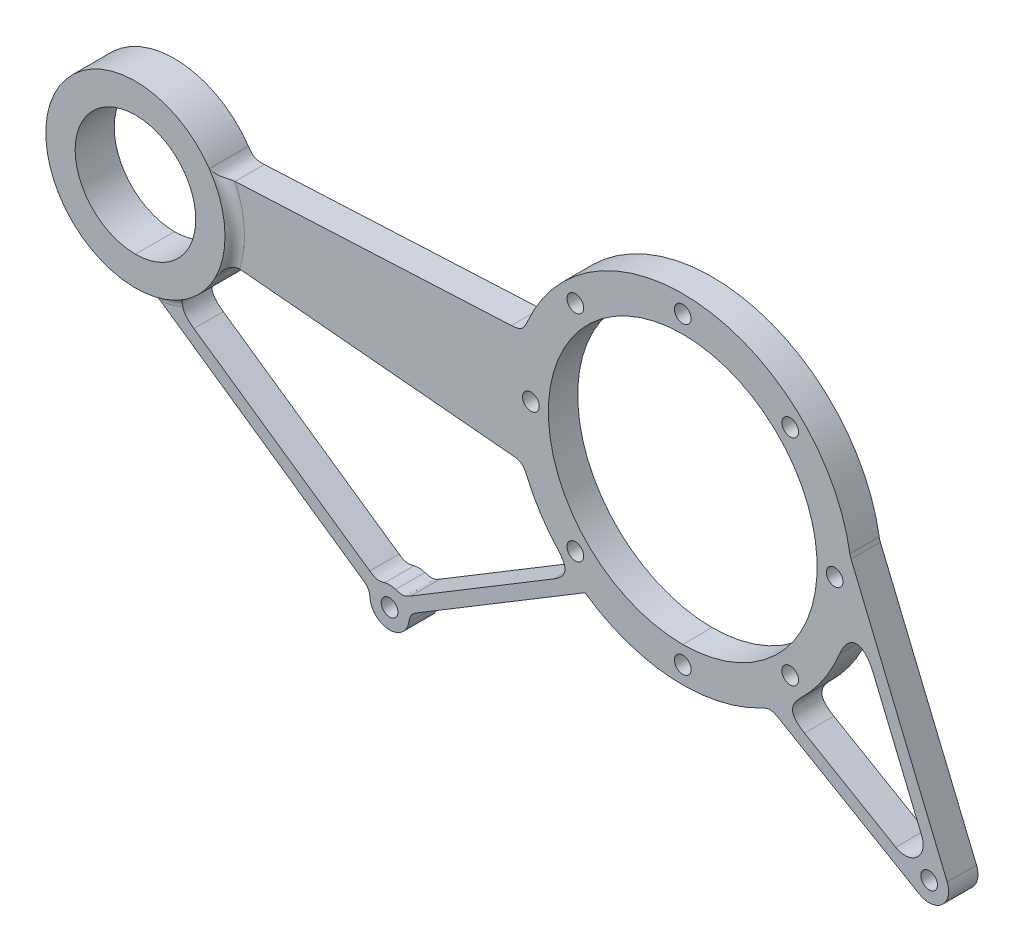
SolidWorks part; units mm, degrees
material "6061-T6 (SS)"
ref_plane "Front Plane" through (0, 0, 0) normal (0, 0, 1) x (1, 0, 0)
ref_plane "Top Plane" through (0, 0, 0) normal (0, 1, 0) x (1, 0, 0)
ref_plane "Right Plane" through (0, 0, 0) normal (1, 0, 0) x (0, 0, -1)
sketch "Sketch1" plane through (0, 0, 0) normal (0, 0, 1) x (1, 0, 0)
  line L0 (-329.0358, 136.1378) -> (-124.1059, 166.9079)
  line L1 (-343.7594, 72.9056) -> (-234.0298, -3.2296)
  line L2 (-223.6766, -3.5577) -> (-149.0272, 41.5159)
  line L3 (-114.3, 88.9) -> (-114.3, 101.6) construction
  line L4 (-53.3056, 126.9173) -> (-9.4675, 21.3025)
  line L5 (-23.0618, 9.4221) -> (-78.8665, 41.9532)
  circle A0 centre (-114.3, 88.9) radius 82.9716 construction
  circle A1 centre (-228.6, -20.8038) radius 12.7 construction
  circle A2 centre (0, 0) radius 12.7 construction
  circle A3 centre (-323.85, 101.6) radius 114 construction
  circle A4 centre (-323.85, 101.6) radius 23.5
  circle A5 centre (-114.3, 101.6) radius 52.3875
  arc A6 (-142.4404, 41.8555) -> (-85.4371, 42.2012) centre (-114.3, 101.6) ccw
  circle A7 centre (-323.85, 101.6) radius 34.925
  arc A8 (-223.6766, -3.5577) -> (-234.0298, -3.2296) centre (-228.6, 4.5962) cw
  arc A9 (-9.4675, 21.3025) -> (-23.0618, 9.4221) centre (-18.2648, 17.651) cw
  circle A10 centre (-228.6, 4.5962) radius 3.2512
  circle A11 centre (-18.2648, 17.651) radius 3.2512
  arc A12 (-142.4404, 41.8555) -> (-149.0272, 41.5159) centre (-145.4168, 35.5364) ccw
  arc A13 (-78.8665, 41.9532) -> (-85.4371, 42.2012) centre (-82.3843, 35.9187) ccw
  circle A14 centre (-114.3, 101.6) radius 66.04 construction
  arc A15 (-124.1059, 166.9079) -> (-53.3056, 126.9173) centre (-114.3, 101.6) cw
  dimension "D1" = 88.9
  dimension "D2" = 12.7
  dimension "D3" = 25.4
  dimension "D4" = 25.4
  dimension "D8" = 165.9433
  dimension "D9" = 228
  dimension "D10" = 47
  dimension "D12" = 104.775
  dimension "D14" = 132.08
  dimension "D15" = 69.85
  dimension "D16" = 9.525
  dimension "D18" = 9.525
  dimension "D20" = 6.5024
  dimension "D21" = 6.5024
  dimension "D23" = 6.985
  dimension "D24" = 6.985
  dimension "D25" = 66.04
  dimension "D5" = 228.6
  dimension "D6" = 20.8038
  dimension "D7" = 114.3
  dimension "D11" = 12.7
  dimension "D13" = 209.55
  dimension "D17" = 25.4
  dimension "D19" = 25.4
  dimension "D22" = 17.651
extrude "Boss-Extrude1" add sketch "Sketch1" along normal blind 11.43 contours A7 A4 | A8 L2 A6 L0 A7 L1 A10 | A6 A5 | A9 L4 A6 L5 A11 region at (-187.4243, 81.6254, 0) region at (-301.706, 127.3172, 0)
ref_point "Point4"
sketch "Sketch5" plane through (0, 0, 11.43) normal (0, 0, 1) x (1, 0, 0)
  circle A0 centre (-323.85, 101.6) radius 23.5
  circle A1 centre (-323.85, 101.6) radius 34.925
  circle A4 centre (-323.85, 101.6) radius 23.5 construction
  arc A5 (-329.0358, 136.1378) -> (-343.7594, 72.9056) centre (-323.85, 101.6) ccw construction
extrude "Boss-Extrude4" add sketch "Sketch5" along normal blind 3.81
ref_plane "Plane1" through (-114.3, 101.6, 0) normal (-1, 0, 0) x (0, 0, 1)
ref_plane "Plane2" through (-323.85, 0, 0) normal (-1, 0, 0) x (0, 0, 1)
split line "Split Line1"
split line "Split Line2"
sketch "Sketch8" plane through (0, 0, 11.43) normal (0, 0, 1) x (1, 0, 0)
  line L0 (-114.3, 101.6) -> (-114.3, 160.8137) construction
  circle A0 centre (-114.3, 101.6) radius 59.2137 construction
  circle A1 centre (-114.3, 160.8137) radius 3.2512
  circle A2 centre (-72.4296, 143.4704) radius 3.2512
  circle A3 centre (-55.0862, 101.6) radius 3.2512
  circle A4 centre (-72.4296, 59.7296) radius 3.2512
  circle A5 centre (-114.3, 42.3863) radius 3.2512
  circle A6 centre (-156.1704, 59.7296) radius 3.2512
  circle A7 centre (-173.5137, 101.6) radius 3.2512
  circle A8 centre (-156.1704, 143.4704) radius 3.2512
  point P22 (-114.3, 101.6)
  dimension "D1" = 118.4275
  dimension "D2" = 6.5024
  dimension "D3" = 8
extrude "Cut-Extrude3" cut sketch "Sketch8" against normal through all both and the other way through all
sketch "Sketch9" plane through (0, 0, 0) normal (0, 0, -1) x (-1, 0, 0)
  line L0 (48.4248, 96.938) -> (21.1243, 31.1656)
  line L1 (31.2747, 22.2949) -> (75.5642, 48.1133)
  line L2 (18.2648, 17.651) -> (64.5869, 44.6542) construction
  line L3 (23.0618, 9.4221) -> (78.8665, 41.9532) construction
  line L4 (53.3056, 126.9173) -> (9.4675, 21.3025) construction
  line L5 (18.2648, 17.651) -> (30.1686, 46.3295) construction
  line L6 (11.227, 20.5722) -> (49.028, 111.6426)
  line L7 (22.1024, 11.0679) -> (80.2923, 44.9894)
  line L8 (53.3056, 126.9173) -> (9.4675, 21.3025)
  line L9 (78.8665, 41.9532) -> (23.0618, 9.4221)
  arc A0 (53.3056, 126.9173) -> (49.028, 111.6426) centre (114.3, 101.6) ccw
  arc A1 (85.4371, 42.2012) -> (142.4404, 41.8555) centre (114.3, 101.6) ccw construction
  arc A2 (80.2923, 44.9894) -> (85.4371, 42.2012) centre (114.3, 101.6) ccw
  arc A4 (48.4248, 96.938) -> (75.5642, 48.1133) centre (114.3, 101.6) ccw
  arc A7 (85.4371, 42.2012) -> (78.8665, 41.9532) centre (82.3843, 35.9187) ccw construction
  arc A8 (11.227, 20.5722) -> (22.1024, 11.0679) centre (18.2648, 17.651) ccw
  arc A9 (78.8665, 41.9532) -> (85.4371, 42.2012) centre (82.3843, 35.9187) cw
  arc A10 (23.0618, 9.4221) -> (9.4675, 21.3025) centre (18.2648, 17.651) cw
  arc A11 (21.1243, 31.1656) -> (31.2747, 22.2949) centre (27.6929, 28.4392) ccw
  point P39 (39.1342, 32.7568)
  point P40 (0, 0)
  dimension "D1" = 7.62
  dimension "D2" = 5.08
  dimension "D4" = 7.112
  dimension "D3" = 5.08
extrude "Cut-Extrude5" cut sketch "Sketch9" against normal up to surface (11.43 mm away) up to face at (-111.0488, 160.8137, 11.43)
sketch "Sketch10" plane through (0, 0, 0) normal (0, 0, -1) x (-1, 0, 0)
  line L0 (323.8812, 77.8778) -> (-49198.7404, -6814.8686) construction
  line L1 (237.8465, 11.0118) -> (309.7494, 60.9012) construction
  line L2 (221.7813, 8.7133) -> (158.5805, 46.8743) construction
  line L3 (152.385, 47.6481) -> (221.137, 6.1352)
  line L4 (322.5609, 66.6988) -> (235.9505, 6.6047)
  line L5 (149.0272, 41.5159) -> (223.6766, -3.5577)
  line L6 (343.7594, 72.9056) -> (234.0298, -3.2296)
  line L8 (315.188, 67.7662) -> (233.0546, 10.7785)
  line L9 (156.7056, 50.9735) -> (223.7628, 10.484)
  line L10 (301.5001, 74.7627) -> (161.3478, 55.2558)
  line L11 (223.6766, -3.5577) -> (149.0272, 41.5159) construction
  line L12 (343.7594, 72.9056) -> (234.0298, -3.2296) construction
  arc A0 (161.3478, 55.2558) -> (156.7056, 50.9735) centre (114.3, 101.6) cw
  circle A2 centre (323.85, 101.6) radius 34.925 construction
  arc A3 (315.188, 67.7662) -> (301.5001, 74.7627) centre (323.85, 101.6) cw
  arc A4 (221.137, 6.1352) -> (235.9505, 6.6047) centre (228.6, 4.5962) ccw
  circle A5 centre (228.6, 4.5962) radius 3.2512 construction
  arc A6 (142.4404, 41.8555) -> (152.385, 47.6481) centre (114.3, 101.6) ccw
  circle A7 centre (323.85, 101.6) radius 23.5 construction
  arc A9 (80.2923, 44.9894) -> (142.4404, 41.8555) centre (114.3, 101.6) ccw construction
  arc A10 (149.0272, 41.5159) -> (142.4404, 41.8555) centre (145.4168, 35.5364) ccw construction
  arc A11 (322.5609, 66.6988) -> (343.7594, 72.9056) centre (323.85, 101.6) ccw
  arc A12 (142.4404, 41.8555) -> (149.0272, 41.5159) centre (145.4168, 35.5364) cw
  arc A13 (233.0546, 10.7785) -> (223.7628, 10.484) centre (228.6, 4.5962) ccw
  arc A14 (223.6766, -3.5577) -> (234.0298, -3.2296) centre (228.6, 4.5962) ccw construction
  arc A15 (223.6766, -3.5577) -> (234.0298, -3.2296) centre (228.6, 4.5962) ccw
  arc A16 (114.3, 49.2125) -> (114.3, 153.9875) centre (114.3, 101.6) ccw construction
  dimension "D1" = 7.62
  dimension "D2" = 66.04
  dimension "D3" = 0
  dimension "D4" = 5.08
  dimension "D5" = 5.08
extrude "Cut-Extrude6" cut sketch "Sketch10" against normal up to surface (11.43 mm away) up to face at (-41.9462, 47.9637, 11.43)
sketch "Sketch12" plane through (0, 0, 0) normal (0, 0, -1) x (-1, 0, 0)
  line L0 (329.0358, 136.1378) -> (124.1059, 166.9079) construction
  line L1 (161.3478, 147.9442) -> (301.5001, 128.4373)
  line L2 (121.5219, 153.4873) -> (327.0896, 124.8756) construction
  line L3 (124.1059, 166.9079) -> (329.0358, 136.1378)
  arc A0 (114.3, 49.2125) -> (114.3, 153.9875) centre (114.3, 101.6) ccw construction
  arc A1 (161.3478, 147.9442) -> (124.1059, 166.9079) centre (114.3, 101.6) ccw
  arc A3 (329.0358, 136.1378) -> (301.5001, 128.4373) centre (323.85, 101.6) ccw
  circle A4 centre (323.85, 101.6) radius 34.925 construction
  circle A6 centre (323.85, 101.6) radius 23.5 construction
  arc A7 (156.7056, 50.9735) -> (161.3478, 55.2558) centre (114.3, 101.6) ccw construction
  dimension "D1" = 0
extrude "Cut-Extrude8" cut sketch "Sketch12" against normal up to surface (11.43 mm away) up to face at (-41.9462, 47.9637, 11.43)
sketch "Sketch15" plane through (0, 0, 0) normal (0, 0, -1) x (-1, 0, 0)
  line L0 (176.5285, 79.489) -> (290.922, 89.9596)
  line L2 (301.5001, 74.7627) -> (161.3478, 55.2558)
  line L3 (161.3478, 147.9442) -> (301.5001, 128.4373)
  line L4 (161.3478, 147.9442) -> (301.5001, 128.4373) construction
  line L5 (176.5285, 123.711) -> (293.0538, 118.0727)
  arc A0 (176.5285, 79.489) -> (161.3478, 55.2558) centre (114.3, 101.6) cw
  arc A2 (290.922, 89.9596) -> (301.5001, 74.7627) centre (323.85, 101.6) ccw
  arc A4 (80.2923, 44.9894) -> (152.385, 47.6481) centre (114.3, 101.6) ccw construction
  circle A5 centre (323.85, 101.6) radius 34.925 construction
  arc A6 (161.3478, 147.9442) -> (176.5285, 123.711) centre (114.3, 101.6) cw
  arc A7 (301.5001, 128.4373) -> (293.0538, 118.0727) centre (323.85, 101.6) ccw
  arc A8 (161.3478, 147.9442) -> (49.028, 111.6426) centre (114.3, 101.6) ccw construction
  dimension "D1" = 8
  dimension "D2" = 16.51
  dimension "D3" = 11.43
extrude "Edge Cut" cut sketch "Sketch15" against normal up to surface (11.43 mm away) up to face at (-114.3, 101.6, 11.43)
fillet "Fillet2" radius 3.81 2 edges at (-289.025, 104.2408, 11.43) (-318.8459, 67.0354, 11.43)
fillet "Fillet1" radius 7.112 15 edges at (-49.028, 111.6426, 5.715) (-176.5285, 123.711, 5.715) (-293.0538, 118.0727, 7.62) (-221.137, 6.1352, 5.715) (-235.9505, 6.6047, 5.715) (-322.5609, 66.6988, 7.62) (-315.188, 67.7662, 7.62) (-290.922, 89.9596, 7.62) (-176.5285, 79.489, 5.715) (-233.0546, 10.7785, 5.715) (-223.7628, 10.484, 5.715) (-156.7056, 50.9735, 5.715) (-80.2923, 44.9894, 5.715) (-75.5642, 48.1133, 5.715) (-48.4248, 96.938, 5.715) conic radius 3.81
